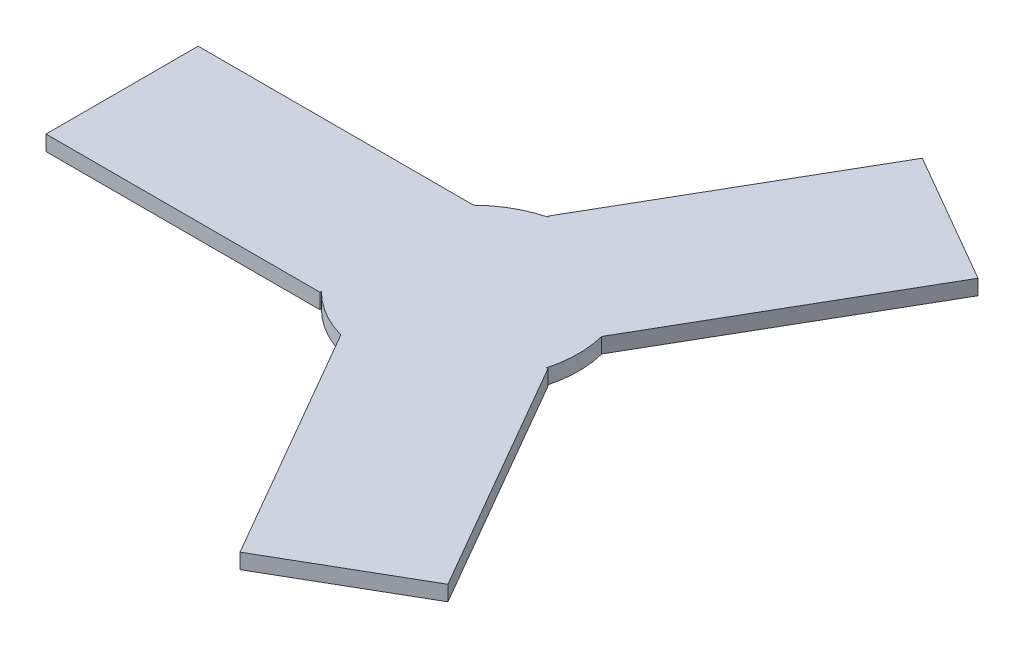
SolidWorks part; units mm, degrees
ref_plane "Plan de face" through (0, 0, 0) normal (0, 0, 1) x (1, 0, 0)
ref_plane "Plan de dessus" through (0, 0, 0) normal (0, 1, 0) x (1, 0, 0)
ref_plane "Plan de droite" through (0, 0, 0) normal (1, 0, 0) x (0, 0, -1)
sketch "Esquisse3" plane through (0, 0, 0) normal (0, 1, 0) x (1, 0, 0)
  line L0 (-150.1573, 0) -> (189.6273, 0) construction
  line L1 (-83.8395, -145.9242) -> (87.7229, 151.2306) construction
  line L2 (-78.0725, 135.2255) -> (117.7517, -203.9519) construction
  line L3 (-125, 131.2995) -> (-125, -153.5705) construction
  line L4 (-25, -25) -> (-115, -25)
  line L6 (-25, 25) -> (-24.4949, 25)
  line L7 (-115, -25) -> (-115, 25)
  line L8 (-25, -25) -> (-115, 25) construction
  line L9 (-25, 25) -> (-115, -25) construction
  line L10 (-24.4949, 25) -> (-115, 25)
  line L11 (33.8981, 8.7132) -> (79.1506, 87.0929)
  line L12 (35.8494, 112.0929) -> (79.1506, 87.0929)
  line L13 (-9.1506, 34.1506) -> (35.8494, 112.0929)
  line L14 (-9.4032, -33.7132) -> (35.8494, -112.0929)
  line L15 (79.1506, -87.0929) -> (35.8494, -112.0929)
  line L16 (34.1506, -9.1506) -> (79.1506, -87.0929)
  line L17 (-24.4949, 25) -> (-25, -25)
  line L18 (-9.1506, 34.1506) -> (33.8981, 8.7132)
  line L19 (-9.4032, -33.7132) -> (34.1506, -9.1506)
  circle A0 centre (0, 0) radius 125
  circle A1 centre (0, 0) radius 35
  circle A2 centre (0, 0) radius 125
  circle A3 centre (0, 0) radius 125
  point P9 (-70, 0)
  point P32 (0, 0)
  dimension "D1" = 250
  dimension "D4" = 70
  dimension "D2" = 120
  dimension "D3" = 120
  dimension "D5" = 10
  dimension "D6" = 50
  dimension "D7" = 90
  dimension "D8" = 3
extrude "Boss.-Extru.3" add sketch "Esquisse3" along normal blind 5 contours A1 L6 L10 L7 L4 L17 | A1 L14 L15 L16 L19 | L19 A1 L18 L17 | A1 L11 L12 L13 L18 | L18 A1 | A1 region at (-73.3157, 0, -0.0007) region at (0, 0, 0) region at (36.6572, 0, 63.4937) region at (14.7041, 0, -24.8843) region at (36.6585, 0, -63.4929)
